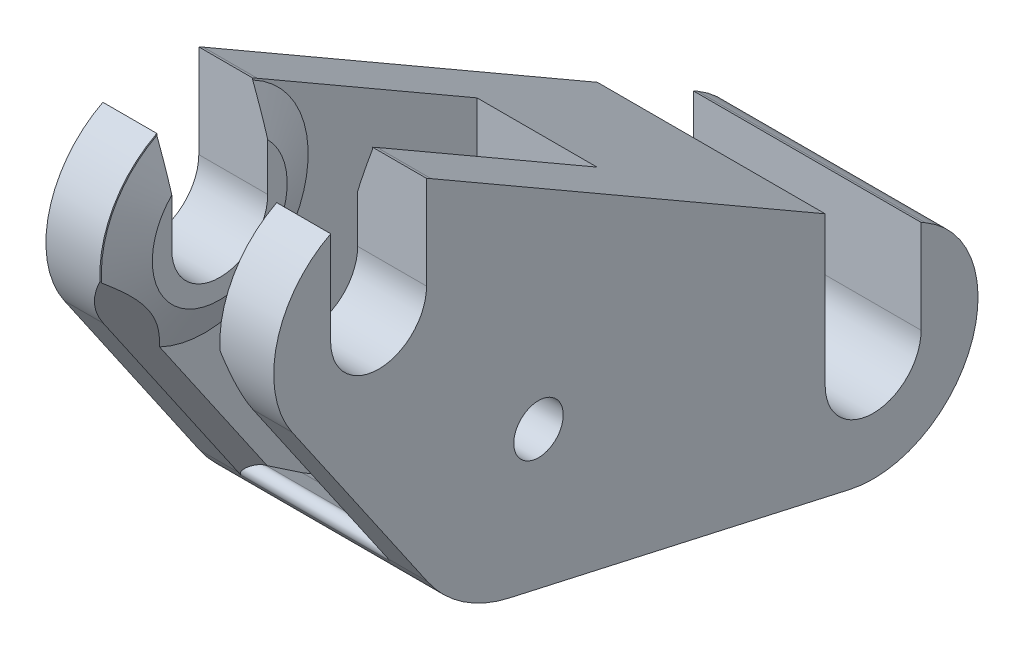
SolidWorks part; units mm, degrees
ref_plane "Front Plane" through (0, 0, 0) normal (0, 0, 1) x (1, 0, 0)
ref_plane "Top Plane" through (0, 0, 0) normal (0, 1, 0) x (1, 0, 0)
ref_plane "Right Plane" through (0, 0, 0) normal (1, 0, 0) x (0, 0, -1)
ref_plane "Plane4" through (15.2, 0, 0) normal (1, 0, 0) x (0, 0, -1)
ref_plane "Plane5" through (7.6, 0, 0) normal (1, 0, 0) x (0, 0, -1)
sketch "Sketch1" plane through (15.2, 0, 0) normal (1, 0, 0) x (0, 0, -1)
  line L0 (3.5235, 220.1706) -> (3.2238, 220.3437)
  line L1 (-32.977, 233.1595) -> (-32.9759, 206.2902) construction
  line L2 (-29.777, 233.1595) -> (-29.777, 239.3852)
  line L3 (-38.7467, 229.1957) -> (-29.7246, 216.0632)
  line L4 (-24.2736, 212.3771) -> (-1.5062, 207.2776)
  line L5 (-36.177, 233.1595) -> (-36.177, 239.3852)
  line L6 (3.2238, 214.1083) -> (3.2238, 220.3437)
  line L7 (-3.1762, 214.1083) -> (-3.1762, 224.0384)
  line L8 (-3.1762, 224.0384) -> (-29.4773, 239.2218)
  arc A0 (-36.177, 239.3852) -> (-38.7467, 229.1957) centre (-32.977, 233.1595) ccw
  arc A1 (3.2238, 214.1083) -> (-3.1762, 214.1083) centre (0.0238, 214.1083) cw
  arc A2 (-29.777, 233.1595) -> (-36.177, 233.1595) centre (-32.977, 233.1595) cw
  arc A3 (-1.5062, 207.2776) -> (3.5235, 220.1706) centre (0.0238, 214.1083) ccw
  arc A4 (-29.4773, 239.2218) -> (-29.777, 239.3852) centre (-32.977, 233.1595) ccw
  circle A6 centre (-22.3065, 221.1595) radius 1.65
  arc A7 (-29.7246, 216.0632) -> (-24.2736, 212.3771) centre (-22.3065, 221.1595) ccw
  dimension "D1" = 3.3
  dimension "D2" = 6.4
  dimension "D3" = 7
  dimension "D8" = 9
  dimension "D4" = 38.1051
  dimension "D5" = 60
  dimension "D6" = 10.67
  dimension "D7" = 12
extrude "Boss-Extrude1" add sketch "Sketch1" against normal blind 15.2
ref_axis "Axis1" through (0, 214.1083, -0.0238) along (1, 0, 0)
sketch "Sketch4" plane through (7.6, 0, 0) normal (1, 0, 0) x (0, 0, -1)
  line L0 (-39.3964, 223.6179) -> (-26.4931, 214.9367)
  line L1 (-14.8065, 221.1595) -> (-14.8065, 244.6595)
  line L2 (-14.8065, 244.6595) -> (-32.977, 244.6595)
  arc A0 (-26.4931, 214.9367) -> (-14.8065, 221.1595) centre (-22.3065, 221.1595) ccw
  circle A1 centre (-22.3065, 221.1595) radius 1.65 construction
  circle A2 centre (-22.3065, 221.1595) radius 5 construction
  circle A3 centre (-32.977, 233.1595) radius 9.5 construction
  arc A4 (-32.977, 244.6595) -> (-39.3964, 223.6179) centre (-32.977, 233.1595) ccw
  dimension "D1" = 2.5
  dimension "D2" = 19
  dimension "D3" = 10
  dimension "D4" = 2
extrude "Cut-Extrude2" cut sketch "Sketch4" against normal blind 4 and the other way blind 4
sketch "Sketch6" plane through (3.6, 0, 0) normal (1, 0, 0) x (0, 0, -1)
  circle A0 centre (-22.3065, 221.1595) radius 2.6
  circle A1 centre (-22.3065, 221.1595) radius 1.65
  dimension "D1" = 5.2
extrude "Boss-Extrude4" add sketch "Sketch6" along normal blind 2
fillet "Fillet5" radius 0.5 1 edges at (7.6, 218.0113, 31.0629)
chamfer "Chamfer3" distance 1 angle 45 2 edges at (11.6, 222.6295, 34.2356) (3.6, 222.6295, 34.2356) tangent propagation no
sketch "Sketch7" plane through (3.6, 0, 0) normal (1, 0, 0) x (0, 0, -1)
  line L0 (-36.177, 233.1595) -> (-36.177, 236.3233)
  line L2 (-29.777, 236.3233) -> (-29.777, 233.1595)
  arc A0 (-36.177, 233.1595) -> (-29.777, 233.1595) centre (-32.977, 233.1595) ccw
  arc A1 (-36.177, 236.3233) -> (-29.777, 236.3233) centre (-32.977, 233.1595) ccw
  dimension "D1" = 4.5
extrude "Boss-Extrude5" add sketch "Sketch7" along normal blind 1
mirror "Mirror1" about plane through (7.6, 0, 0) normal (1, 0, 0) of "Boss-Extrude5", "Boss-Extrude4"
chamfer "Chamfer4" distance 2.4 distance2 1 1 edges at (3.6, 228.6595, 32.977) first distance on face at (3.6, 221.1595, 19.7065)
chamfer "Chamfer5" distance 1 distance2 2.4 1 edges at (11.6, 228.6595, 32.977) first distance on face at (11.1, 232.4914, 32.977)
